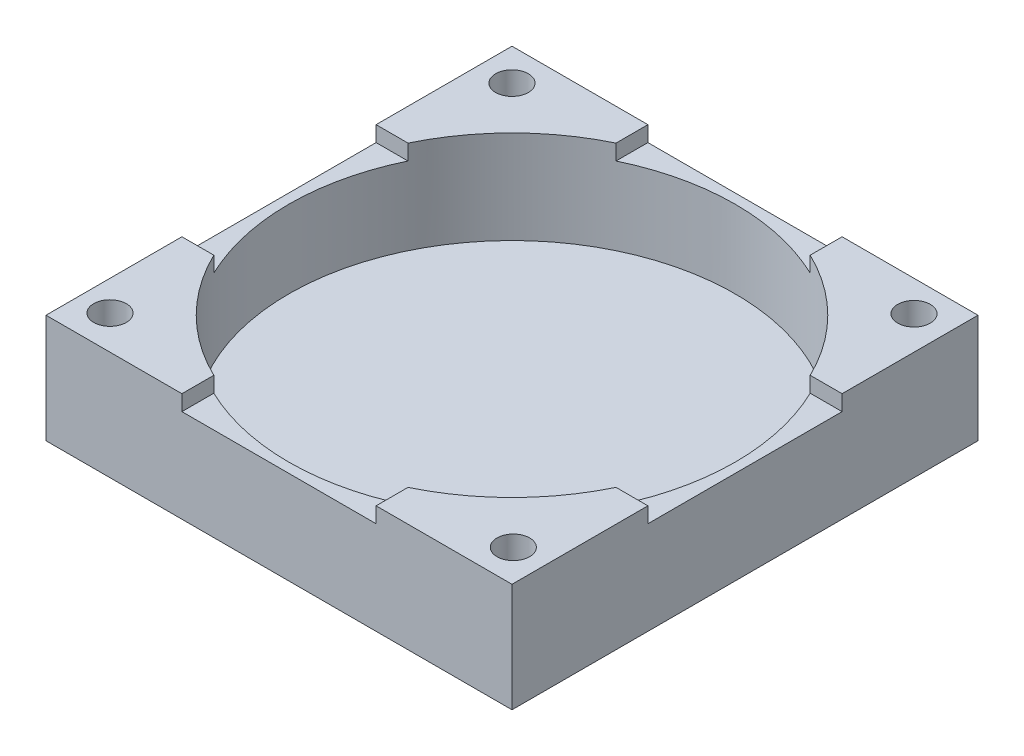
SolidWorks part; units mm, degrees
ref_plane "Front Plane" through (0, 0, 0) normal (0, 0, 1) x (1, 0, 0)
ref_plane "Top Plane" through (0, 0, 0) normal (0, 1, 0) x (1, 0, 0)
ref_plane "Right Plane" through (0, 0, 0) normal (1, 0, 0) x (0, 0, -1)
sketch "Sketch1" plane through (0, 0, 0) normal (0, 1, 0) x (1, 0, 0)
  line L1 (-30, -30) -> (30, -30)
  line L2 (-30, -30) -> (-30, 30)
  line L3 (-30, 30) -> (30, 30)
  line L4 (30, -30) -> (30, 30)
  line L5 (-30, -30) -> (30, 30) construction
  line L6 (-30, 30) -> (30, -30) construction
  circle A1 centre (0, 0) radius 28.75
  circle A2 centre (-25.8801, 25.8801) radius 2.1
  circle A3 centre (-26.1208, -25.6372) radius 2.1
  circle A4 centre (25.9644, -25.7956) radius 2.1
  circle A5 centre (25.7138, 26.0454) radius 2.1
  point P0 (0, 0)
  dimension "D1" = 36.6
  dimension "D3" = 4.2
  dimension "D4" = 4.2
  dimension "D5" = 4.2
  dimension "D6" = 4.2
  dimension "D9" = 60
  dimension "D10" = 57.5
  dimension "D2" = 36.6
  dimension "D7" = 36.6
  dimension "D8" = 36.6
other "AlignGroup1"
extrude "Boss-Extrude4" add sketch "Sketch1" along normal blind 14
extrude "Boss-Extrude5" add sketch "Sketch1<8>" along normal blind 2 contours A1 region at (0, 0, 0)
sketch "Sketch1<8>" plane through (0, 0, 0) normal (0, 1, 0) x (1, 0, 0) same geometry as "Sketch1"
sketch "Sketch5" plane through (0, 14, 0) normal (0, 1, 0) x (1, 0, 0)
  line L0 (-12.5, 30) -> (-12.5, 25.8904)
  line L1 (30, 30) -> (-30, 30) construction
  line L2 (12.5, 30) -> (12.5, 25.8904)
  line L3 (30, 12.5) -> (25.8904, 12.5)
  line L4 (30, -30) -> (30, 30) construction
  line L5 (25.8904, -12.5) -> (30, -12.5)
  line L6 (12.5, -30) -> (12.5, -25.8904)
  line L7 (-30, -30) -> (30, -30) construction
  line L8 (-12.5, -30) -> (-12.5, -25.8904)
  line L9 (0, 0) -> (0, 12.6575) construction
  line L10 (0, 0) -> (15.9647, 0) construction
  line L11 (-30, 12.5) -> (-25.8904, 12.5)
  line L12 (-30, 30) -> (-30, -30) construction
  line L13 (-30, -12.5) -> (-25.8904, -12.5)
  line L14 (-30, 30) -> (-30, -30) construction
  line L15 (-12.5, 30) -> (12.5, 30)
  line L16 (30, 12.5) -> (30, -12.5)
  line L17 (12.5, -30) -> (-12.5, -30)
  line L18 (-30, -12.5) -> (-30, 12.5)
  circle A0 centre (0, 0) radius 28.75 construction
  circle A1 centre (0, 0) radius 28.75 construction
  arc A2 (-25.8904, 12.5) -> (-25.8904, -12.5) centre (0, 0) ccw
  arc A3 (12.5, 25.8904) -> (-12.5, 25.8904) centre (0, 0) ccw
  arc A4 (25.8904, -12.5) -> (25.8904, 12.5) centre (0, 0) ccw
  arc A5 (-12.5, -25.8904) -> (12.5, -25.8904) centre (0, 0) ccw
  dimension "D1" = 25
  dimension "D2" = 25
extrude "Cut-Extrude2" cut sketch "Sketch5" against normal blind 2 contours L2 A1 L0 L11 | L11 L5 A0 L3 | L8 L6 L11 | L11 A2 L13 L18 region at (0, 14, -29.7466) region at (27.9452, 14, -12.2466) region at (0, 14, 29.0034)
